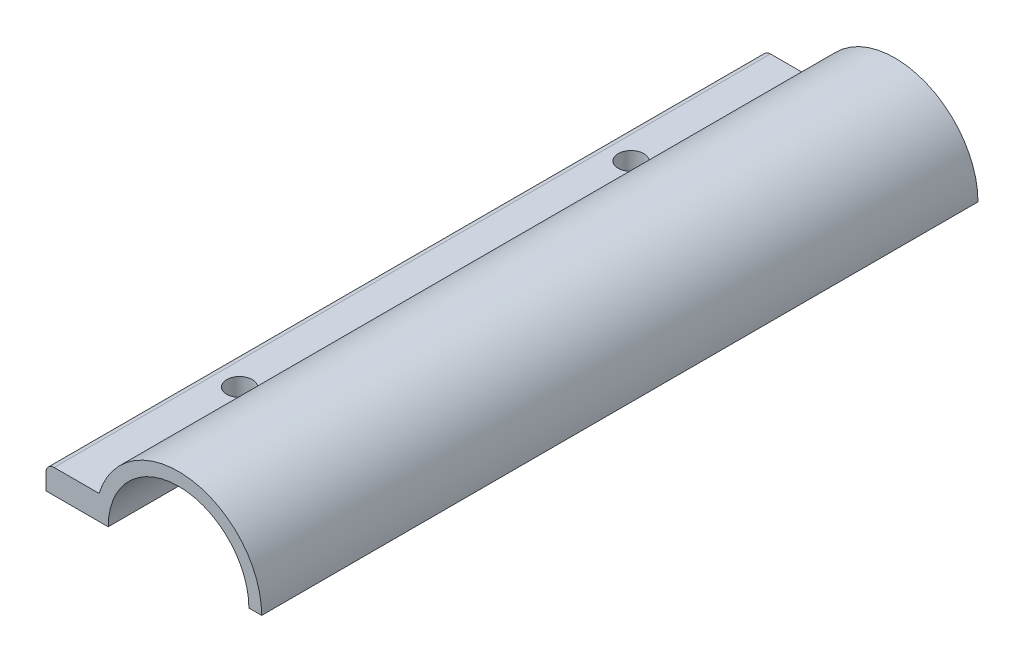
SolidWorks part; units mm, degrees
material "ABS"
ref_plane "X-Y Datum" through (0, 0, 0) normal (0, 0, 1) x (1, 0, 0)
ref_plane "X-Z Datum" through (0, 0, 0) normal (0, 1, 0) x (1, 0, 0)
ref_plane "Y-Z Datum" through (0, 0, 0) normal (1, 0, 0) x (0, 0, -1)
sketch "Sketch1" plane through (0, 0, 0) normal (0, 0, 1) x (1, 0, 0)
  line L0 (-13, 0) -> (-20.7245, 0)
  line L1 (-20.7245, 0) -> (-20.7245, -13)
  line L2 (-20.7245, -13) -> (0, -13)
  line L3 (-13, 0) -> (13, 0)
  line L4 (0, 13) -> (-20.7245, 13)
  line L5 (-20.7245, 13) -> (-20.7245, 0)
  line L6 (-20.7245, 3.81) -> (-12.4292, 3.81)
  circle A0 centre (0, 0) radius 13
  circle A1 centre (0, 0) radius 11
  dimension "D3" = 2
  dimension "D2" = 22
  dimension "D1" = 7.7245
  dimension "D4" = 3.81
extrude "Boss-Extrude1" add sketch "Sketch1" along normal blind 112 contours A1 L3 A0 | A0 L6 L5 L0 region at (-12.569, 1.8832, 0) region at (-16.7661, 1.9278, 0)
sketch "Sketch3" plane through (0, 3.81, 0) normal (0, 1, 0) x (1, 0, 0)
  circle A0 centre (-15.8622, -25.4) radius 2 construction
  circle A1 centre (-15.8622, -86.6) radius 2 construction
  circle A2 centre (-15.8622, -25.4) radius 2
  circle A3 centre (-15.8622, -86.6) radius 2
extrude "Cut-Extrude2" cut sketch "Sketch3" against normal through all
fillet "Fillet1" radius 1.27 1 edges at (-20.7245, 3.81, 56)
